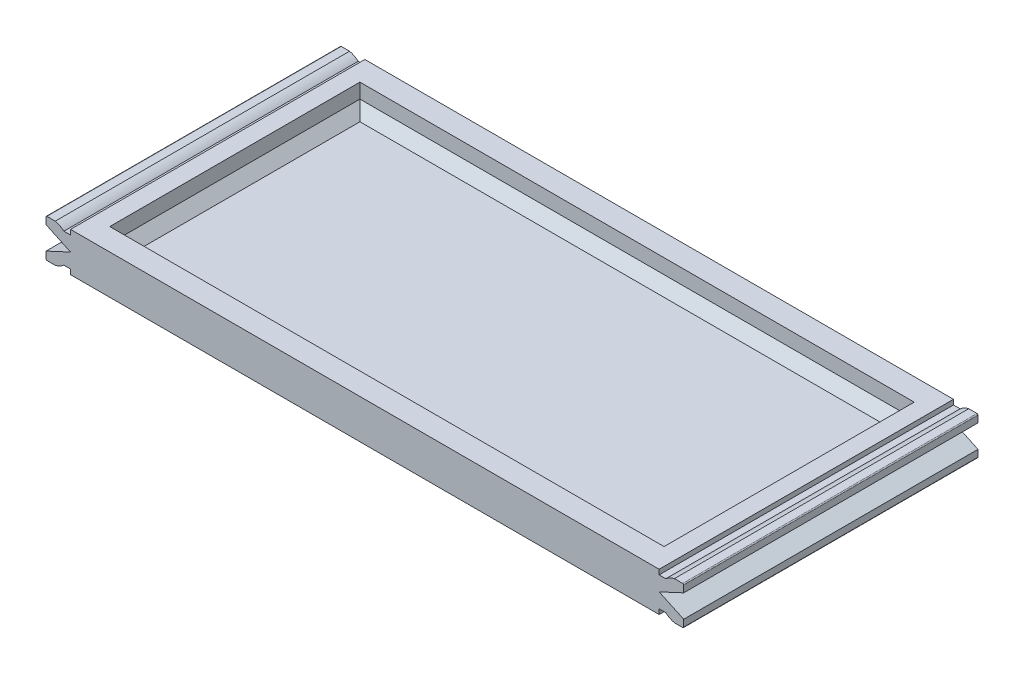
SolidWorks part; units mm, degrees
ref_plane "前视基准面" through (0, 0, 0) normal (0, 0, 1) x (1, 0, 0)
ref_plane "上视基准面" through (0, 0, 0) normal (0, 1, 0) x (1, 0, 0)
ref_plane "右视基准面" through (0, 0, 0) normal (1, 0, 0) x (0, 0, -1)
sketch "草图1" plane through (0, 0, 0) normal (0, 1, 0) x (1, 0, 0)
  line L0 (30, 15) -> (30, -15)
  line L1 (30, 15) -> (-30, 15)
  line L2 (30, -15) -> (-30, -15)
  line L3 (-30, 15) -> (-30, -15)
  line L4 (30, 15) -> (-30, -15) construction
  line L5 (30, -15) -> (-30, 15) construction
  point P1 (0, 0)
  dimension "D1" = 30
  dimension "D2" = 60
extrude "凸台-拉伸1" add sketch "草图1" along normal blind 2 and the other way blind 2
sketch "草图2" plane through (0, 2, 0) normal (0, 1, 0) x (1, 0, 0)
  line L0 (28.25, 12.75) -> (28.25, -12.75)
  line L1 (28.25, 12.75) -> (-28.25, 12.75)
  line L2 (28.25, -12.75) -> (-28.25, -12.75)
  line L3 (-28.25, 12.75) -> (-28.25, -12.75)
  line L4 (28.25, 12.75) -> (-28.25, -12.75) construction
  line L5 (28.25, -12.75) -> (-28.25, 12.75) construction
  point P1 (0, 0)
  dimension "D1" = 25.5
  dimension "D2" = 56.5
extrude "切除-拉伸1" cut sketch "草图2" against normal blind 2.5
chamfer "倒角1" distance 1 angle 45 4 edges at (28.25, -0.5, 0) (0, -0.5, 12.75) (-28.25, -0.5, 0) (0, -0.5, -12.75)
sketch "草图3" plane through (0, 0, 0) normal (0, 0, 1) x (1, 0, 0)
  line L0 (30, 0) -> (32, 0) construction
  line L1 (30, -2) -> (30, 2) construction
  line L2 (32, 0) -> (32.5, 0) construction
  line L3 (30, 1.5) -> (30, 0)
  line L4 (30, 1.5) -> (30.6771, 1.5)
  line L5 (32.5, 1.1658) -> (32.5, 1.95)
  line L6 (32.5, 1.95) -> (31.5556, 1.95)
  line L7 (30, 0) -> (32.5, 1.1658)
  arc A0 (31.5556, 1.95) -> (30.6771, 1.5) centre (32, 0) ccw
  dimension "D5" = 2
  dimension "D1" = 2
  dimension "D2" = 0.5
  dimension "D3" = 1.5
  dimension "D4" = 1.95
  dimension "D6" = 25
  dimension "D7" = 1.1658
extrude "凸台-拉伸2" add sketch "草图3" along normal blind 15 and the other way blind 15 contours L6 A0 L4 L7 L5 region at (31.1553, 1.1423, 0)
mirror "镜向1" about plane through (0, 0, 0) normal (0, 1, 0) of "凸台-拉伸2"
mirror "镜向2" about plane through (0, 0, 0) normal (1, 0, 0) of "镜向1", "凸台-拉伸2"
fillet "圆角1" radius 0.1 4 edges at (32.5, -1.95, 0) (32.5, 1.95, 0) (-32.5, -1.95, 0) (-32.5, 1.95, 0)
